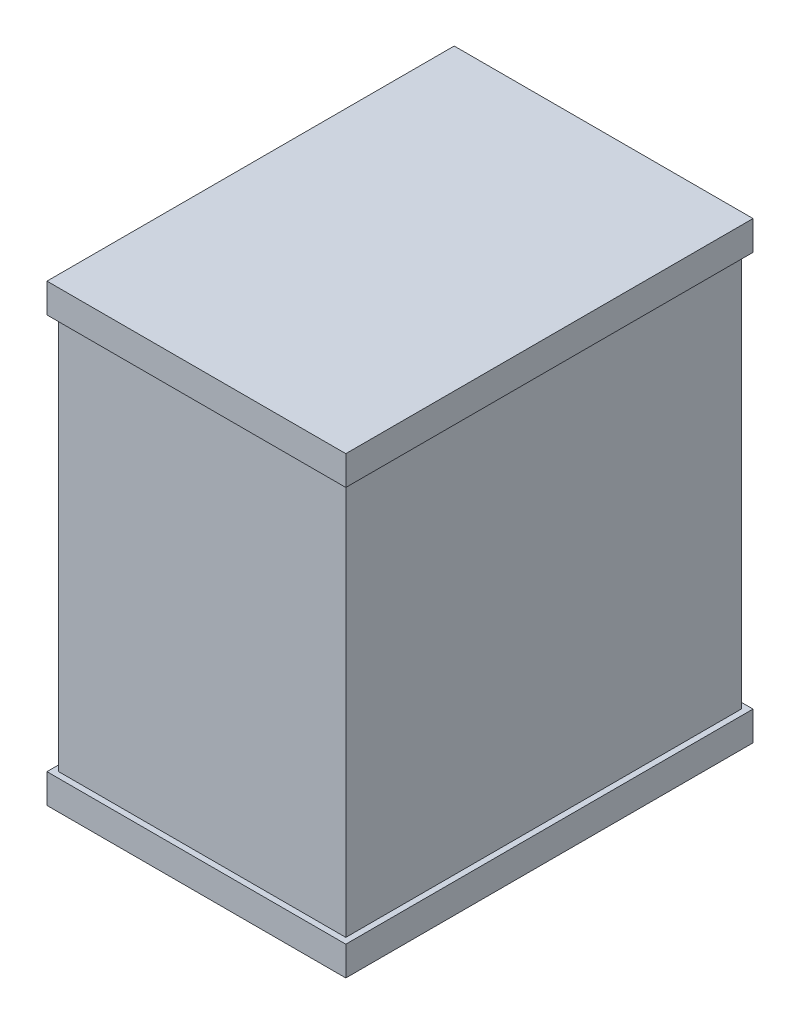
SolidWorks part; units mm, degrees
ref_plane "前视基准面" through (0, 0, 0) normal (0, 0, 1) x (1, 0, 0)
ref_plane "上视基准面" through (0, 0, 0) normal (0, 1, 0) x (1, 0, 0)
ref_plane "右视基准面" through (0, 0, 0) normal (1, 0, 0) x (0, 0, -1)
sketch "草图1" plane through (0, 0, 0) normal (0, 0, 1) x (1, 0, 0)
  line L1 (-49, -77.5) -> (49, -77.5)
  line L2 (-49, -77.5) -> (-49, 77.5)
  line L3 (-49, 77.5) -> (49, 77.5)
  line L4 (49, -77.5) -> (49, 77.5)
  line L5 (-49, -77.5) -> (49, 77.5) construction
  line L6 (-49, 77.5) -> (49, -77.5) construction
  point P0 (0, 0)
  dimension "D1" = 98
  dimension "D2" = 155
extrude "凸台-拉伸1" add sketch "草图1" along normal blind 135
sketch "草图4" plane through (0, 77.5, 0) normal (0, 1, 0) x (1, 0, 0)
  line L0 (51, 2) -> (-51, 2)
  line L1 (-51, 2) -> (-51, -137)
  line L2 (-51, -137) -> (51, -137)
  line L3 (51, -137) -> (51, 2)
  line L4 (49, 0) -> (-49, 0)
  line L5 (-49, 0) -> (-49, -135)
  line L6 (-49, -135) -> (49, -135)
  line L7 (49, -135) -> (49, 0)
  line L8 (49, 0) -> (-49, 0)
  line L9 (-49, 0) -> (-49, -135)
  line L10 (-49, -135) -> (49, -135)
  line L11 (49, -135) -> (49, 0)
  dimension "D1" = 0
  dimension "D2" = 2
extrude "凸台-拉伸3" add sketch "草图4" against normal blind 10
sketch "草图5" plane through (0, -77.5, 0) normal (0, -1, 0) x (1, 0, 0)
  line L0 (-51, -2) -> (51, -2)
  line L1 (51, -2) -> (51, 137)
  line L2 (51, 137) -> (-51, 137)
  line L3 (-51, 137) -> (-51, -2)
  line L4 (-49, 0) -> (49, 0)
  line L5 (49, 0) -> (49, 135)
  line L6 (49, 135) -> (-49, 135)
  line L7 (-49, 135) -> (-49, 0)
  line L8 (-49, 0) -> (49, 0)
  line L9 (49, 0) -> (49, 135)
  line L10 (49, 135) -> (-49, 135)
  line L11 (-49, 135) -> (-49, 0)
  dimension "D1" = 0
  dimension "D2" = 2
extrude "凸台-拉伸4" add sketch "草图5" against normal blind 10
